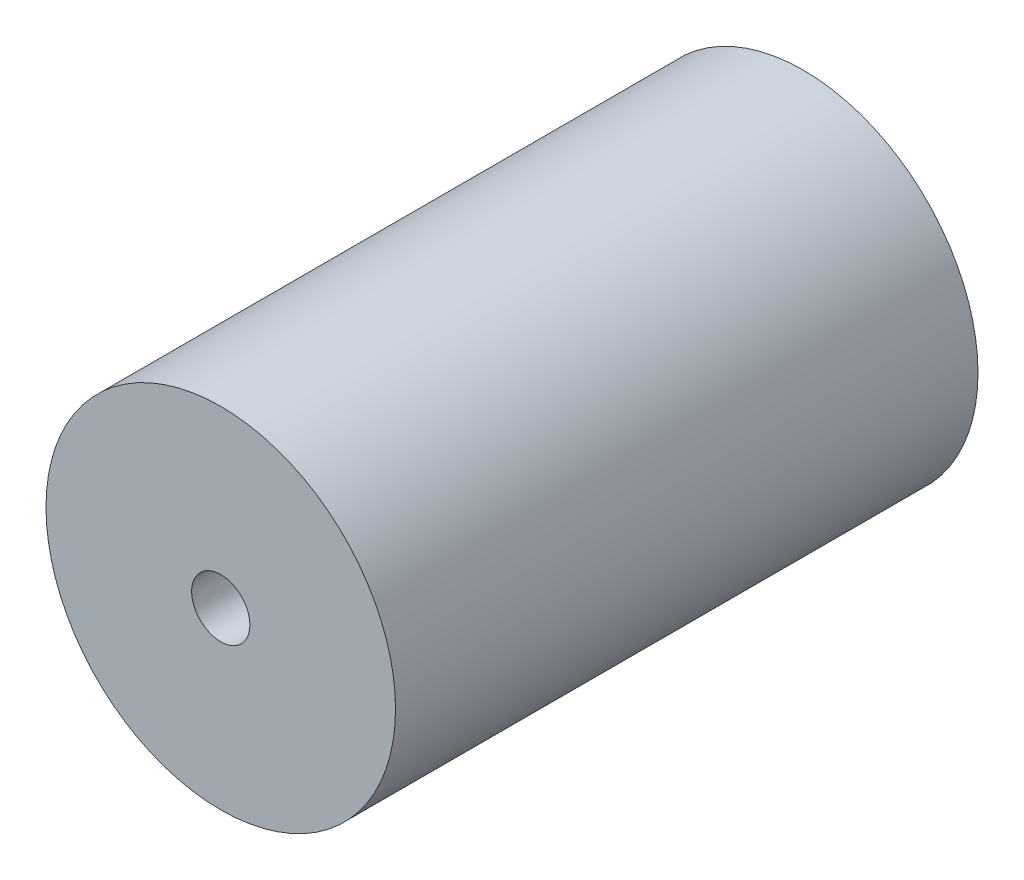
SolidWorks part; units mm, degrees
material "Cast Alloy Steel"
ref_plane "Front Plane" through (0, 0, 0) normal (0, 0, 1) x (1, 0, 0)
ref_plane "Top Plane" through (0, 0, 0) normal (0, 1, 0) x (1, 0, 0)
ref_plane "Right Plane" through (0, 0, 0) normal (1, 0, 0) x (0, 0, -1)
sketch "Sketch2" plane through (0, 0, 0) normal (0, 0, 1) x (1, 0, 0)
  circle A0 centre (0, 0) radius 18
extrude "Boss-Extrude1" add sketch "Sketch2" along normal blind 30 and the other way blind 30
sketch "Sketch3" plane through (0, 0, 30) normal (0, 0, 1) x (1, 0, 0)
  circle A0 centre (0, 0) radius 3
  dimension "D1" = 0
extrude "Cut-Extrude1" cut sketch "Sketch3" against normal blind 60
